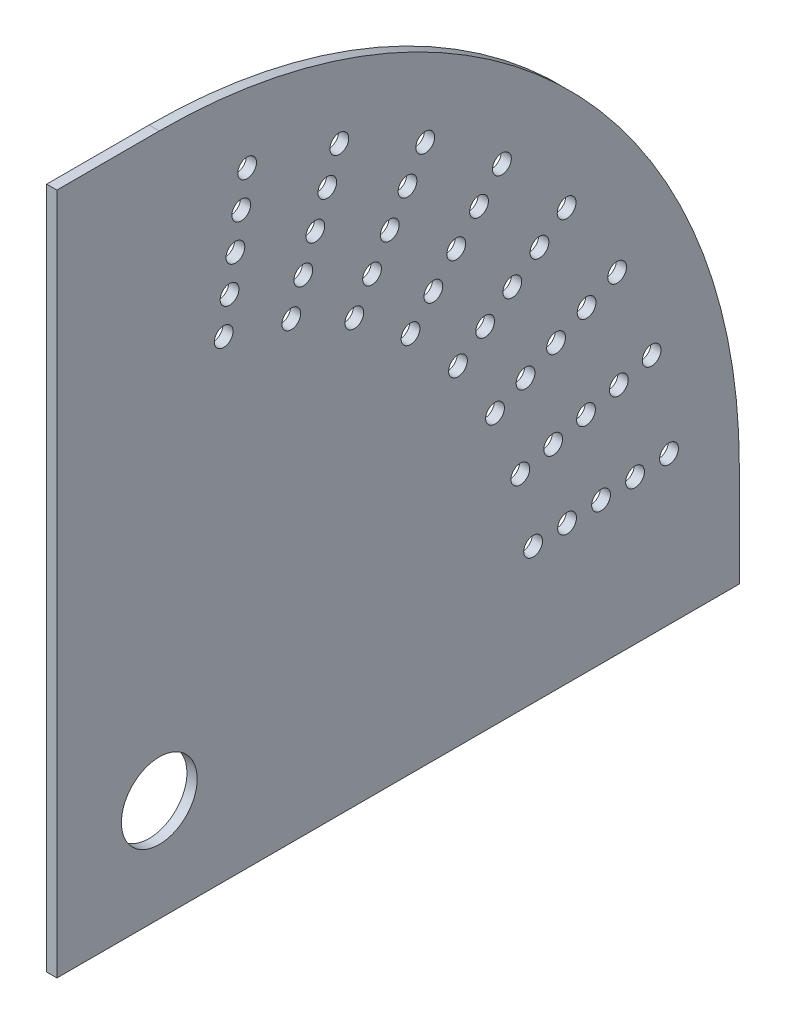
SolidWorks part; units mm, degrees
ref_plane "Front Plane" through (0, 0, 0) normal (0, 0, 1) x (1, 0, 0)
ref_plane "Top Plane" through (0, 0, 0) normal (0, 1, 0) x (1, 0, 0)
ref_plane "Right Plane" through (0, 0, 0) normal (1, 0, 0) x (0, 0, -1)
sketch "Sketch1" plane through (0, 0, 0) normal (1, 0, 0) x (0, 0, -1)
  line L1 (0, 0) -> (200, 0)
  line L2 (0, 0) -> (0, 200)
  line L3 (0, 200) -> (200, 200)
  line L4 (200, 0) -> (200, 200)
  circle A0 centre (30, 30) radius 11.11
  dimension "D1" = 200
  dimension "D5" = 22.22
  dimension "D2" = 200
  dimension "D3" = 30
  dimension "D4" = 30
extrude "Boss-Extrude1" add sketch "Sketch1" along normal blind 3
sketch "Sketch2" plane through (3, 0, 0) normal (1, 0, 0) x (0, 0, -1)
  line L0 (200, 0) -> (200, 200) construction
  line L1 (200, 200) -> (0, 200) construction
  line L2 (30, 200) -> (0, 200)
  line L3 (0, 200) -> (0, 0) construction
  line L4 (0, 200) -> (3.7965, 239.3342)
  line L5 (3.7965, 239.3342) -> (230.7646, 219.6671)
  line L6 (230.7646, 219.6671) -> (249.4864, 45.6174)
  line L7 (249.4864, 45.6174) -> (200, 30)
  arc A0 (200, 30) -> (30, 200) centre (30, 30) ccw
  point P12 (0, 0)
  point P15 (0, 0)
extrude "Cut-Extrude1" cut sketch "Sketch2" against normal blind 3
sketch "Sketch3" plane through (3, 0, 0) normal (1, 0, 0) x (0, 0, -1)
  line L0 (55.7448, 177.7742) -> (30, 30) construction
  circle A0 centre (55.7448, 177.7742) radius 2.75
  circle A1 centre (54.0284, 167.9226) radius 2.75
  circle A2 centre (52.3121, 158.071) radius 2.75
  circle A3 centre (50.5958, 148.2193) radius 2.75
  circle A4 centre (48.8795, 138.3677) radius 2.75
  dimension "D1" = 5.5
  dimension "D3" = 10
  dimension "D2" = 150
  dimension "D4" = 10
  dimension "D5" = 10
  dimension "D6" = 10
extrude "Cut-Extrude2" cut sketch "Sketch3" against normal blind 3 contours A0 | A1 | A2 | A3 | A4
pattern_circular "CirPattern1" count 8 over 75 about axis through (3, 30, -30) along (-1, 0, 0) of "Cut-Extrude2"
